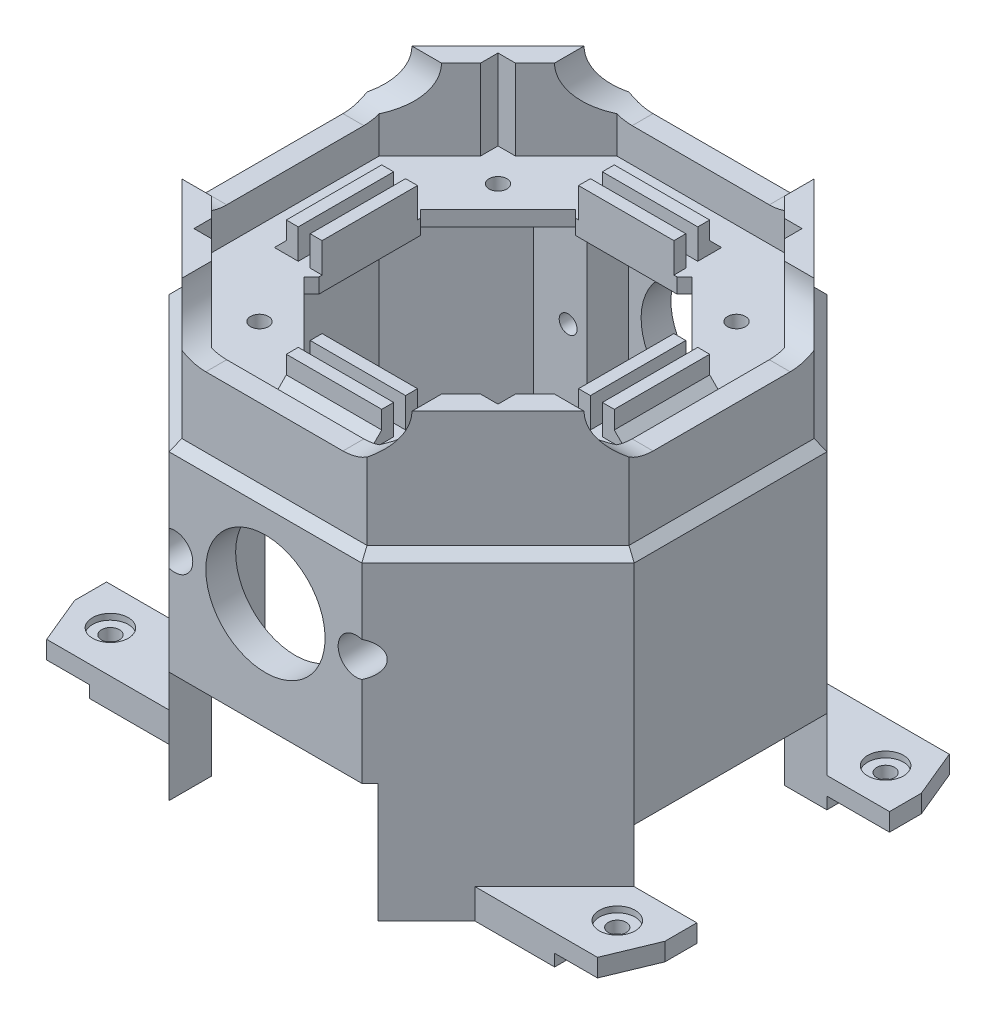
SolidWorks part; units mm, degrees
ref_plane "Front Plane" through (0, 0, 0) normal (0, 0, 1) x (1, 0, 0)
ref_plane "Top Plane" through (0, 0, 0) normal (0, 1, 0) x (1, 0, 0)
ref_plane "Right Plane" through (0, 0, 0) normal (1, 0, 0) x (0, 0, -1)
sketch "Sketch1" plane through (0, 0, 0) normal (0, 1, 0) x (1, 0, 0)
  line L1 (15.533, 37.5) -> (-15.533, 37.5)
  line L2 (-15.533, 37.5) -> (-37.5, 15.533)
  line L3 (-37.5, 15.533) -> (-37.5, -15.533)
  line L4 (-37.5, -15.533) -> (-15.533, -37.5)
  line L5 (-15.533, -37.5) -> (15.533, -37.5)
  line L6 (15.533, -37.5) -> (37.5, -15.533)
  line L7 (37.5, -15.533) -> (37.5, 15.533)
  line L8 (37.5, 15.533) -> (15.533, 37.5)
  circle A0 centre (0, 0) radius 37.5 construction
  dimension "D1" = 75
extrude "Boss-Extrude1" add sketch "Sketch1" along normal blind 40
sketch "Sketch7" plane through (0, 0, 0) normal (0, -1, 0) x (1, 0, 0)
  line L0 (-15.533, 37.5) -> (15.533, 37.5) construction
  line L1 (39, 16.1543) -> (16.1543, 39)
  line L2 (16.1543, 39) -> (-16.1543, 39)
  line L3 (-16.1543, 39) -> (-39, 16.1543)
  line L4 (-39, 16.1543) -> (-39, -16.1543)
  line L5 (-39, -16.1543) -> (-16.1543, -39)
  line L6 (-16.1543, -39) -> (16.1543, -39)
  line L7 (16.1543, -39) -> (39, -16.1543)
  line L8 (39, -16.1543) -> (39, 16.1543)
  circle A0 centre (0, 0) radius 39 construction
  dimension "76" = 78
extrude "Boss-Extrude4" add sketch "Sketch7" along normal blind 55
sketch "Sketch18" plane through (0, 40, 0) normal (0, 1, 0) x (1, 0, 0)
  line L0 (-39, -16.1543) -> (-39, 16.1543) construction
  line L2 (-39, 7.5) -> (-39, -7.5)
  line L12 (-39, 7.5) -> (-33, 7.5)
  line L14 (-33, 7.5) -> (-33, -7.5)
  line L15 (-33, -7.5) -> (-39, -7.5)
  line L16 (0, -55) -> (0, 55) construction
  line L17 (33, 7.5) -> (33, -7.5)
  line L18 (39, 7.5) -> (33, 7.5)
  line L19 (39, 7.5) -> (39, -7.5)
  line L20 (33, -7.5) -> (39, -7.5)
  point P1 (-33, 0)
  dimension "D1" = 15
  dimension "D2" = 6
  dimension "D3" = 6
sketch "Sketch3" plane through (0, 0, 37.5) normal (0, 0, 1) x (1, 0, 0)
  line L0 (-11.5, 18) -> (11.5, 18) construction
  line L1 (-11.5, 25.8) -> (11.5, 25.8)
  line L2 (-11.5, 10.2) -> (11.5, 10.2)
  line L4 (-15.533, 40) -> (15.533, 40) construction
  arc A0 (-11.5, 25.8) -> (-11.5, 10.2) centre (-11.5, 18) ccw
  arc A1 (11.5, 10.2) -> (11.5, 25.8) centre (11.5, 18) ccw
  point P2 (0, 18)
  dimension "D1" = 7.8
  dimension "D2" = 23
  dimension "D3" = 22
extrude "Cut-Extrude1" cut sketch "Sketch3" against normal up to surface (75 mm away) up to face at (0, 20, -37.5)
sketch "Sketch4" plane through (-37.5, 0, 0) normal (-1, 0, 0) x (0, 0, 1)
  line L0 (-11.5, 18) -> (11.5, 18) construction
  line L1 (-11.5, 25.8) -> (11.5, 25.8)
  line L2 (-11.5, 10.2) -> (11.5, 10.2)
  line L4 (-15.533, 40) -> (15.533, 40) construction
  arc A0 (-11.5, 25.8) -> (-11.5, 10.2) centre (-11.5, 18) ccw
  arc A1 (11.5, 10.2) -> (11.5, 25.8) centre (11.5, 18) ccw
  point P2 (0, 18)
  dimension "D1" = 7.8
  dimension "D2" = 22
  dimension "D3" = 23
extrude "Cut-Extrude2" cut sketch "Sketch4" against normal up to surface and the other way up to surface up to face at (39, -27.5, 0) other way up to face at (-39, -27.5, 0)
chamfer "Chamfer5" distance 3 angle 45 8 edges at (-39, 0, 0) (-27.5772, 0, -27.5772) (0, 0, -39) (27.5772, 0, -27.5772) (39, 0, 0) (27.5772, 0, 27.5772) (0, 0, 39) (-27.5772, 0, 27.5772)
shell "Shell1" [suppressed] thickness 2
sketch "Sketch11" plane through (0, 0, -39) normal (0, 0, 1) x (1, 0, 0)
  line L1 (16.1543, -55) -> (-16.1543, -55) construction
  circle A0 centre (0, -17) radius 10
  dimension "D2" = 20
  dimension "D1" = 38
extrude "Cut-Extrude5" cut sketch "Sketch11" along normal up to surface (78 mm away) up to face at (0, -29, 39)
chamfer "Chamfer7" distance 3 angle 45 8 edges at (37.5, 40, 0) (26.5165, 40, 26.5165) (0, 40, 37.5) (-26.5165, 40, 26.5165) (-37.5, 40, 0) (26.5165, 40, -26.5165) (-26.5165, 40, -26.5165) (0, 40, -37.5)
extrude "Boss-Extrude10" add sketch "Sketch18" along normal blind 50 and the other way up to vertex (14.2 mm away) separate body
sketch "Sketch20" plane through (0, 90, 0) normal (0, 1, 0) x (1, 0, 0)
  line L1 (-39, 7.5) -> (39, 7.5)
  line L2 (-39, 7.5) -> (-39, -7.5)
  line L3 (-39, -7.5) -> (39, -7.5)
  line L4 (39, 7.5) -> (39, -7.5)
extrude "Boss-Extrude11" add sketch "Sketch20" along normal blind 6
chamfer "Chamfer8" distance 3 angle 45 2 edges at (-39, 25.8, 0) (39, 25.8, 0)
chamfer "Chamfer9" distance 1 angle 45 13 edges at (-33, 57.9, -7.5) (0, 90, -7.5) (33, 57.9, -7.5) (-33, 57.9, 7.5) (0, 90, 7.5) (33, 57.9, 7.5) (39, 62.4, -7.5) (0, 96, -7.5) (-39, 62.4, -7.5) (-39, 96, 0) (39, 62.4, 7.5) (0, 96, 7.5) (-39, 62.4, 7.5)
sketch "Sketch21" plane through (0, 0, 39) normal (0, 0, 1) x (1, 0, 0)
  line L0 (39, -55) -> (16.1543, -55) construction
  line L1 (-17.5, -35) -> (17.5, -35)
  line L2 (-17.5, -35) -> (-17.5, -55)
  line L3 (-17.5, -55) -> (17.5, -55)
  line L4 (17.5, -35) -> (17.5, -55)
  point P6 (0, -35)
  dimension "D1" = 35
  dimension "D2" = 20
extrude "Cut-Extrude6" cut sketch "Sketch21" against normal up to surface (78 mm away)
sketch "Sketch22" plane through (-39, 0, 0) normal (-1, 0, 0) x (0, 0, 1)
  line L0 (-16.1543, -55) -> (-16.1543, -3) construction
  line L1 (-16.1543, -41) -> (16.1543, -41)
  line L2 (-16.1543, -41) -> (-16.1543, -55)
  line L3 (-16.1543, -55) -> (16.1543, -55)
  line L4 (16.1543, -41) -> (16.1543, -55)
  dimension "D1" = 14
extrude "Cut-Extrude7" cut sketch "Sketch22" against normal up to surface (78 mm away) up to face at (39, -29, 0)
sketch "Sketch23" plane through (0, 96, 0) normal (0, 1, 0) x (1, 0, 0)
  line L0 (39, 16.1543) -> (39, -16.1543) construction
  line L1 (-39, -39) -> (39, -39)
  line L2 (-39, -39) -> (-39, 39)
  line L3 (-39, 39) -> (39, 39)
  line L4 (39, -39) -> (39, 39)
  line L5 (-39, -39) -> (39, 39) construction
  line L6 (-39, 39) -> (39, -39) construction
  line L7 (-16.1543, 39) -> (16.1543, 39) construction
  point P0 (0, 0)
extrude "Cut-Extrude8" [suppressed] cut sketch "Sketch23" against normal up to vertex
sketch "Sketch25" plane through (0, -55, 0) normal (0, -1, 0) x (1, 0, 0)
  line L0 (-39, -16.1543) -> (-49.5, -16.1543)
  line L1 (-42.5, -22.5) -> (42.5, -22.5) construction
  line L2 (-42.5, -22.5) -> (-42.5, 22.5) construction
  line L3 (-42.5, 22.5) -> (42.5, 22.5) construction
  line L4 (42.5, -22.5) -> (42.5, 22.5) construction
  line L5 (-42.5, -22.5) -> (42.5, 22.5) construction
  line L6 (-42.5, 22.5) -> (42.5, -22.5) construction
  line L7 (-49.5, -16.1543) -> (-49.5, -29.5)
  line L8 (-49.5, -29.5) -> (-25.6543, -29.5)
  line L9 (-39, -16.1543) -> (-17.5, -37.6543) construction
  line L12 (-39, -16.1543) -> (-25.6543, -29.5)
  line L13 (55, 0) -> (-55, 0) construction
  line L14 (-39, 16.1543) -> (-49.5, 16.1543)
  line L15 (-49.5, 16.1543) -> (-49.5, 29.5)
  line L16 (-49.5, 29.5) -> (-25.6543, 29.5)
  line L17 (-39, 16.1543) -> (-25.6543, 29.5)
  line L18 (0, -55) -> (0, 55) construction
  line L19 (39, -16.1543) -> (49.5, -16.1543)
  line L20 (49.5, -16.1543) -> (49.5, -29.5)
  line L21 (49.5, -29.5) -> (25.6543, -29.5)
  line L22 (39, -16.1543) -> (25.6543, -29.5)
  line L23 (39, 16.1543) -> (25.6543, 29.5)
  line L24 (49.5, 29.5) -> (25.6543, 29.5)
  line L25 (49.5, 16.1543) -> (49.5, 29.5)
  line L26 (39, 16.1543) -> (49.5, 16.1543)
  circle A0 centre (-42.5, 22.5) radius 1.5
  circle A1 centre (42.5, 22.5) radius 1.5
  circle A2 centre (42.5, -22.5) radius 1.5
  circle A3 centre (-42.5, -22.5) radius 1.5
  point P0 (0, 0)
  dimension "D3" = 3
  dimension "D1" = 85
  dimension "D2" = 45
  dimension "D4" = 7
  dimension "D5" = 7
extrude "Boss-Extrude12" add sketch "Sketch25" against normal blind 5
sketch "Sketch26" plane through (0, 40, 0) normal (0, 1, 0) x (1, 0, 0)
  line L1 (-14.2904, 34.5) -> (14.2904, 34.5)
  line L2 (-14.2904, 34.5) -> (-14.2904, -34.5)
  line L3 (-14.2904, -34.5) -> (14.2904, -34.5)
  line L4 (14.2904, 34.5) -> (14.2904, -34.5)
extrude "Cut-Extrude9" cut sketch "Sketch26" against normal blind 15
sketch "Sketch27" plane through (0, 40, 0) normal (0, 1, 0) x (1, 0, 0)
  line L1 (34.5, 7.5) -> (-34.5, 7.5)
  line L2 (34.5, 7.5) -> (34.5, -7.5)
  line L3 (34.5, -7.5) -> (-34.5, -7.5)
  line L4 (-34.5, 7.5) -> (-34.5, -7.5)
  line L5 (-34.5, 14.2904) -> (-34.5, -14.2904) construction
  line L6 (34.5, -14.2904) -> (34.5, 14.2904) construction
  line L7 (14.2904, -34.5) -> (14.2904, 34.5) construction
  point P10 (14.2904, 0)
  point P11 (34.5, 0)
  dimension "D1" = 15
extrude "Cut-Extrude10" cut sketch "Sketch27" against normal blind 15
chamfer "Chamfer10" distance 8 angle 22.5 4 edges at (49.5, -52.5, 29.5) (49.5, -52.5, -29.5) (-49.5, -52.5, -29.5) (-49.5, -52.5, 29.5)
sketch "Sketch28" plane through (0, -55, 0) normal (0, -1, 0) x (1, 0, 0)
  line L0 (46.1863, 29.5) -> (25.6543, 29.5) construction
  line L1 (39, 29.5) -> (49.5, 29.5)
  line L2 (39, 29.5) -> (39, -29.5)
  line L3 (39, -29.5) -> (49.5, -29.5)
  line L4 (49.5, 29.5) -> (49.5, -29.5)
  line L5 (25.6543, -29.5) -> (46.1863, -29.5) construction
  line L6 (39, -16.1543) -> (39, 16.1543) construction
  line L7 (49.5, 16.1543) -> (49.5, 21.5) construction
  line L8 (0, -42.9) -> (0, 42.9) construction
  line L9 (-39, -29.5) -> (-49.5, -29.5)
  line L10 (-49.5, 29.5) -> (-49.5, -29.5)
  line L11 (-39, 29.5) -> (-49.5, 29.5)
  line L12 (-39, 29.5) -> (-39, -29.5)
extrude "Cut-Extrude11" cut sketch "Sketch28" against normal blind 2
sketch "Sketch35" plane through (0, 96, 0) normal (0, 1, 0) x (1, 0, 0)
  line L0 (39, 16.1543) -> (39, -16.1543) construction
  line L1 (-39, -39) -> (39, -39)
  line L2 (-39, -39) -> (-39, 39)
  line L3 (-39, 39) -> (39, 39)
  line L4 (39, -39) -> (39, 39)
  line L5 (-39, -16.1543) -> (-39, 16.1543) construction
  line L6 (-16.1543, 39) -> (16.1543, 39) construction
  line L7 (16.1543, -39) -> (-16.1543, -39) construction
extrude "Cut-Extrude18" cut sketch "Sketch35" against normal blind 78
sketch "Sketch29" plane through (0, -50, 0) normal (0, 1, 0) x (1, 0, 0)
  circle A0 centre (-42.5, 22.5) radius 3
  circle A1 centre (42.5, 22.5) radius 3
  circle A2 centre (42.5, -22.5) radius 3
  circle A3 centre (-42.5, -22.5) radius 3
  dimension "D1" = 6
extrude "Cut-Extrude12" cut sketch "Sketch29" against normal blind 1
sketch "Sketch39" plane through (0, 0, 0) normal (0, 1, 0) x (-1, 0, 0)
  line L0 (-34, 14.0833) -> (-14.0833, 34)
  line L1 (-14.0833, 34) -> (14.0833, 34)
  line L2 (14.0833, 34) -> (34, 14.0833)
  line L3 (34, 14.0833) -> (34, -14.0833)
  line L4 (34, -14.0833) -> (14.0833, -34)
  line L5 (14.0833, -34) -> (-14.0833, -34)
  line L6 (-14.0833, -34) -> (-34, -14.0833)
  line L7 (-34, -14.0833) -> (-34, 14.0833)
  line L9 (34, 0) -> (-34, 0) construction
  line L13 (0, 34) -> (0, -34) construction
  dimension "D1" = 68
  dimension "D2" = 68
  dimension "D3" = 68
  dimension "D4" = 34
extrude "Cut-Extrude19" cut sketch "Sketch39" along normal up to surface (73 mm away) from surface
sketch "Sketch47" plane through (0, -55, 0) normal (0, -1, 0) x (1, 0, 0)
  line L1 (9.5269, 23) -> (-9.5269, 23)
  line L2 (-9.5269, 23) -> (-23, 9.5269)
  line L3 (-23, 9.5269) -> (-23, -9.5269)
  line L4 (-23, -9.5269) -> (-9.5269, -23)
  line L5 (-9.5269, -23) -> (9.5269, -23)
  line L6 (9.5269, -23) -> (23, -9.5269)
  line L7 (23, -9.5269) -> (23, 9.5269)
  line L8 (23, 9.5269) -> (9.5269, 23)
  line L9 (-14.0833, 34) -> (14.0833, 34) construction
  line L11 (14.0833, 34) -> (-14.0833, 34)
  line L12 (-14.0833, 34) -> (-34, 14.0833)
  line L13 (-34, 14.0833) -> (-34, -14.0833)
  line L14 (-34, -14.0833) -> (-14.0833, -34)
  line L15 (-14.0833, -34) -> (14.0833, -34)
  line L16 (14.0833, -34) -> (34, -14.0833)
  line L17 (34, -14.0833) -> (34, 14.0833)
  line L18 (34, 14.0833) -> (14.0833, 34)
  circle A0 centre (0, 0) radius 23 construction
  circle A1 centre (0, 0) radius 34 construction
  dimension "D1" = 11
extrude "Boss-Extrude16" add sketch "Sketch47" against normal blind 2.5 from offset 57 offset against normal yes
chamfer "Chamfer13" distance 10 angle 45 4 edges at (-34, 2, 0) (0, 2, -34) (34, 2, 0) (0, 2, 34)
sketch "Sketch48" plane through (0, 2, 0) normal (0, -1, 0) x (1, 0, 0)
  line L1 (-20, -20) -> (20, -20) construction
  line L2 (-20, -20) -> (-20, 20) construction
  line L3 (-20, 20) -> (20, 20) construction
  line L4 (20, -20) -> (20, 20) construction
  line L5 (-20, -20) -> (20, 20) construction
  line L6 (-20, 20) -> (20, -20) construction
  circle A0 centre (-20, 20) radius 1.5
  circle A1 centre (20, 20) radius 1.5
  circle A2 centre (20, -20) radius 1.5
  circle A3 centre (-20, -20) radius 1.5
  point P0 (0, 0)
  dimension "D1" = 3
  dimension "D2" = 40
extrude "Cut-Extrude22" cut sketch "Sketch48" against normal up to surface (2.5 mm away) up to face at (0, 4.5, 0)
sketch "Sketch49" plane through (0, 4.5, 0) normal (0, 1, 0) x (1, 0, 0)
  line L1 (-25.5, -25.5) -> (25.5, -25.5)
  line L2 (-25.5, -25.5) -> (-25.5, 25.5)
  line L3 (-25.5, 25.5) -> (25.5, 25.5)
  line L4 (25.5, -25.5) -> (25.5, 25.5)
  line L5 (-25.5, -25.5) -> (25.5, 25.5) construction
  line L6 (-25.5, 25.5) -> (25.5, -25.5) construction
  point P0 (0, 0)
  dimension "D1" = 51
extrude "Cut-Extrude23" cut sketch "Sketch49" along normal up to surface (13.5 mm away) up to face at (-25.2791, 18, -25.2791)
sketch "Sketch51" plane through (0, 2, 0) normal (0, 1, 0) x (1, 0, 0)
  line L0 (25.5, 8) -> (27.5, 8)
  line L1 (-25.5, -25.5) -> (25.5, -25.5) construction
  line L2 (-25.5, -25.5) -> (-25.5, 25.5) construction
  line L3 (-25.5, 25.5) -> (25.5, 25.5) construction
  line L4 (25.5, -25.5) -> (25.5, 25.5) construction
  line L5 (-25.5, -25.5) -> (25.5, 25.5) construction
  line L6 (-25.5, 25.5) -> (25.5, -25.5) construction
  line L7 (-8, 25.5) -> (8, 25.5)
  line L8 (-8, 25.5) -> (-8, 27.5)
  line L9 (-8, 27.5) -> (8, 27.5)
  line L10 (8, 25.5) -> (8, 27.5)
  line L11 (-8, 23.5) -> (8, 23.5)
  line L12 (-8, 23.5) -> (-8, 21.5)
  line L13 (-8, 21.5) -> (8, 21.5)
  line L14 (8, 23.5) -> (8, 21.5)
  line L15 (25.5, 8) -> (25.5, -8)
  line L16 (25.5, -8) -> (27.5, -8)
  line L17 (27.5, 8) -> (27.5, -8)
  line L18 (23.5, 8) -> (21.5, 8)
  line L19 (23.5, 8) -> (23.5, -8)
  line L20 (23.5, -8) -> (21.5, -8)
  line L21 (21.5, 8) -> (21.5, -8)
  line L22 (8, -25.5) -> (8, -27.5)
  line L23 (8, -25.5) -> (-8, -25.5)
  line L24 (-8, -25.5) -> (-8, -27.5)
  line L25 (8, -27.5) -> (-8, -27.5)
  line L26 (8, -23.5) -> (8, -21.5)
  line L27 (8, -23.5) -> (-8, -23.5)
  line L28 (-8, -23.5) -> (-8, -21.5)
  line L29 (8, -21.5) -> (-8, -21.5)
  line L30 (-25.5, -8) -> (-27.5, -8)
  line L31 (-25.5, -8) -> (-25.5, 8)
  line L32 (-25.5, 8) -> (-27.5, 8)
  line L33 (-27.5, -8) -> (-27.5, 8)
  line L34 (-23.5, -8) -> (-21.5, -8)
  line L35 (-23.5, -8) -> (-23.5, 8)
  line L36 (-23.5, 8) -> (-21.5, 8)
  line L37 (-21.5, -8) -> (-21.5, 8)
  point P0 (0, 0)
  point P14 (0, 27.5)
  point P15 (0, 21.5)
  point P43 (0, 0)
  dimension "D1" = 51
  dimension "D2" = 16
  dimension "D3" = 2
  dimension "D4" = 2
  dimension "D5" = 4
extrude "Boss-Extrude17" add sketch "Sketch51" along normal blind 7.5
chamfer "Chamfer14" distance 2 angle 45 8 edges at (-23, 3.25, -8) (23, 3.25, -8) (23, 3.25, 8) (8, 3.25, -23) (-8, 3.25, -23) (-23, 3.25, 8) (-8, 3.25, 23) (8, 3.25, 23)
chamfer "Chamfer15" distance 2 angle 45 4 edges at (0, 4.5, -27.5) (27.5, 4.5, 0) (0, 4.5, 27.5) (-27.5, 4.5, 0)
sketch "Sketch55" plane through (0, -35, 0) normal (0, -1, 0) x (1, 0, 0)
  line L0 (-21.0833, 27) -> (-12.0833, 27)
  line L1 (21.0833, 27) -> (14.0833, 34)
  line L2 (14.0833, 34) -> (12.0833, 34)
  line L3 (-14.0833, 34) -> (-21.0833, 27)
  line L4 (-12.0833, 34) -> (-12.0833, 27)
  line L5 (12.0833, 34) -> (12.0833, 27)
  line L6 (-12.0833, 34) -> (-14.0833, 34)
  line L7 (12.0833, 27) -> (21.0833, 27)
  line L8 (40.15, 0) -> (-40.15, 0) construction
  line L9 (12.0833, -27) -> (21.0833, -27)
  line L10 (-12.0833, -34) -> (-14.0833, -34)
  line L11 (12.0833, -34) -> (12.0833, -27)
  line L12 (-12.0833, -34) -> (-12.0833, -27)
  line L13 (-14.0833, -34) -> (-21.0833, -27)
  line L14 (14.0833, -34) -> (12.0833, -34)
  line L15 (21.0833, -27) -> (14.0833, -34)
  line L16 (-21.0833, -27) -> (-12.0833, -27)
  line L18 (-34, 14.0833) -> (-24.0416, 24.0416) construction
  point P22 (0, 0)
  point P23 (0, 0)
  point P24 (0, 0)
  dimension "D1" = 2
  dimension "D2" = 2
  dimension "D3" = 7
extrude "Boss-Extrude19" add sketch "Sketch55" against normal up to vertex (95 mm away)
sketch "Sketch52" plane through (0, 0, 39) normal (0, 0, 1) x (1, 0, 0)
  circle A0 centre (15.24, -17) radius 1.5
  circle A1 centre (-15.24, -17) radius 1.5
  point P4 (15.24, -17)
  point P5 (-15.24, -17)
  dimension "D3" = 3
extrude "Cut-Extrude24" cut sketch "Sketch52" against normal up to surface (78 mm away) up to face at (10, -17, -39)
sketch "Sketch56" plane through (0, 0, 39) normal (0, 0, 1) x (1, 0, 0)
  circle A0 centre (-15.24, -17) radius 3.05
  circle A1 centre (15.24, -17) radius 3.05
  dimension "D1" = 6.1
extrude "Cut-Extrude25" cut sketch "Sketch56" against normal blind 8
sketch "Sketch57" plane through (0, 0, -39) normal (0, 0, -1) x (-1, 0, 0)
  circle A0 centre (-15.24, -17) radius 3.05
  circle A1 centre (15.24, -17) radius 3.05
  dimension "D1" = 6.1
extrude "Cut-Extrude26" cut sketch "Sketch57" against normal blind 8
